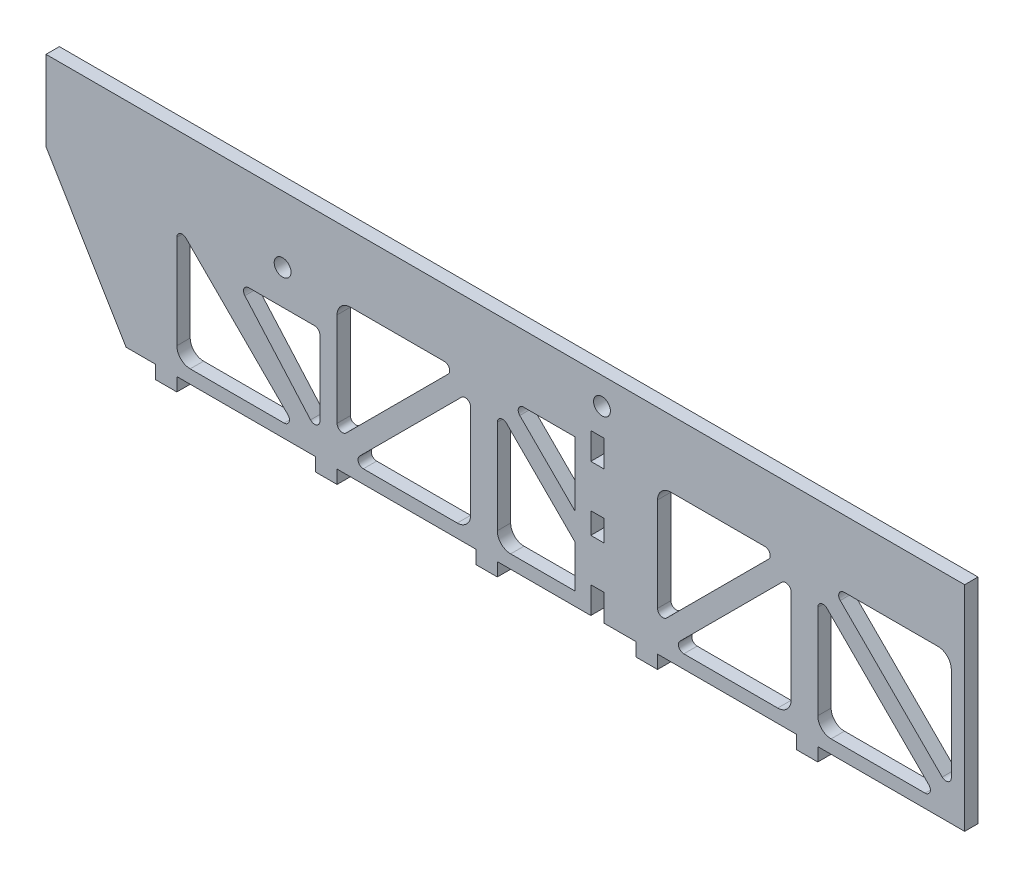
SolidWorks part; units mm, degrees
material "Pine"
ref_plane "Front Plane" through (0, 0, 0) normal (0, 0, 1) x (1, 0, 0)
ref_plane "Top Plane" through (0, 0, 0) normal (0, 1, 0) x (1, 0, 0)
ref_plane "Right Plane" through (0, 0, 0) normal (1, 0, 0) x (0, 0, -1)
sketch "Model" plane through (0, 0, 0) normal (0, 0, 1) x (1, 0, 0)
  line L0 (-306.6281, 15.625) -> (-306.6281, 51.1493)
  line L1 (-309.1681, 53.6893) -> (-340.406, 53.6893)
  line L2 (-342.3135, 49.472) -> (-311.0755, 13.9477)
  line L8 (-171.2321, 6.35) -> (-215.9, 6.35)
  line L9 (-222.25, 57.3679) -> (-222.25, 12.7)
  line L10 (-217.9139, 59.1639) -> (-169.4361, 10.6861)
  line L11 (-234.95, 57.3679) -> (-234.95, 12.7)
  line L12 (-241.3, 6.35) -> (-285.9679, 6.35)
  line L13 (-239.2861, 59.1639) -> (-287.7639, 10.6861)
  line L14 (-294.1139, 17.0361) -> (-245.6361, 65.5139)
  line L15 (-298.45, 63.5) -> (-298.45, 18.8321)
  line L16 (-247.4321, 69.85) -> (-292.1, 69.85)
  line L17 (-323.6321, 6.35) -> (-368.3, 6.35)
  line L18 (-374.65, 57.3679) -> (-374.65, 12.7)
  line L19 (-370.3139, 59.1639) -> (-321.8361, 10.6861)
  line L20 (-18.8321, 6.35) -> (-63.5, 6.35)
  line L21 (-69.85, 57.3679) -> (-69.85, 12.7)
  line L22 (-17.0361, 10.6861) -> (-65.5139, 59.1639)
  line L23 (-82.55, 57.3679) -> (-82.55, 12.7)
  line L24 (-88.9, 6.35) -> (-133.5679, 6.35)
  line L25 (-86.8861, 59.1639) -> (-135.3639, 10.6861)
  line L26 (-93.2361, 65.5139) -> (-141.7139, 17.0361)
  line L27 (-146.05, 63.5) -> (-146.05, 18.8321)
  line L28 (-95.0321, 69.85) -> (-139.7, 69.85)
  line L29 (-163.0861, 17.0361) -> (-211.5639, 65.5139)
  line L30 (-165.1, 69.85) -> (-209.7679, 69.85)
  line L31 (-158.75, 63.5) -> (-158.75, 18.8321)
  line L35 (-398.78, 0) -> (-436.88, 63.5)
  line L36 (0, 0) -> (-398.78, 0)
  line L37 (0, 0) -> (0, 95.25)
  line L38 (0, 95.25) -> (-436.88, 95.25)
  line L39 (-436.88, 63.5) -> (-436.88, 95.25)
  line L40 (-6.35, 63.5) -> (-6.35, 18.8321)
  line L41 (-59.1639, 65.5139) -> (-10.6861, 17.0361)
  line L42 (-12.7, 69.85) -> (-57.3679, 69.85)
  arc A0 (-222.25, 12.7) -> (-215.9, 6.35) centre (-215.9, 12.7) ccw
  arc A1 (-217.9139, 59.1639) -> (-222.25, 57.3679) centre (-219.71, 57.3679) ccw
  arc A2 (-171.2321, 6.35) -> (-169.4361, 10.6861) centre (-171.2321, 8.89) ccw
  arc A3 (-234.95, 57.3679) -> (-239.2861, 59.1639) centre (-237.49, 57.3679) ccw
  arc A4 (-241.3, 6.35) -> (-234.95, 12.7) centre (-241.3, 12.7) ccw
  arc A5 (-287.7639, 10.6861) -> (-285.9679, 6.35) centre (-285.9679, 8.89) ccw
  arc A6 (-245.6361, 65.5139) -> (-247.4321, 69.85) centre (-247.4321, 67.31) ccw
  arc A7 (-298.45, 18.8321) -> (-294.1139, 17.0361) centre (-295.91, 18.8321) ccw
  arc A8 (-292.1, 69.85) -> (-298.45, 63.5) centre (-292.1, 63.5) ccw
  arc A9 (-323.6321, 6.35) -> (-321.8361, 10.6861) centre (-323.6321, 8.89) ccw
  arc A10 (-374.65, 12.7) -> (-368.3, 6.35) centre (-368.3, 12.7) ccw
  arc A11 (-370.3139, 59.1639) -> (-374.65, 57.3679) centre (-372.11, 57.3679) ccw
  arc A12 (-69.85, 12.7) -> (-63.5, 6.35) centre (-63.5, 12.7) ccw
  arc A13 (-65.5139, 59.1639) -> (-69.85, 57.3679) centre (-67.31, 57.3679) ccw
  arc A14 (-18.8321, 6.35) -> (-17.0361, 10.6861) centre (-18.8321, 8.89) ccw
  arc A15 (-82.55, 57.3679) -> (-86.8861, 59.1639) centre (-85.09, 57.3679) ccw
  arc A16 (-88.9, 6.35) -> (-82.55, 12.7) centre (-88.9, 12.7) ccw
  arc A17 (-135.3639, 10.6861) -> (-133.5679, 6.35) centre (-133.5679, 8.89) ccw
  arc A18 (-93.2361, 65.5139) -> (-95.0321, 69.85) centre (-95.0321, 67.31) ccw
  arc A19 (-146.05, 18.8321) -> (-141.7139, 17.0361) centre (-143.51, 18.8321) ccw
  arc A20 (-139.7, 69.85) -> (-146.05, 63.5) centre (-139.7, 63.5) ccw
  arc A21 (-163.0861, 17.0361) -> (-158.75, 18.8321) centre (-161.29, 18.8321) ccw
  arc A22 (-209.7679, 69.85) -> (-211.5639, 65.5139) centre (-209.7679, 67.31) ccw
  arc A23 (-158.75, 63.5) -> (-165.1, 69.85) centre (-165.1, 63.5) ccw
  arc A24 (-306.6281, 15.625) -> (-311.0755, 13.9477) centre (-309.1681, 15.625) cw
  arc A25 (-340.406, 53.6893) -> (-342.3135, 49.472) centre (-340.406, 51.1493) ccw
  arc A26 (-306.6281, 51.1493) -> (-309.1681, 53.6893) centre (-309.1681, 51.1493) ccw
  arc A27 (-10.6861, 17.0361) -> (-6.35, 18.8321) centre (-8.89, 18.8321) ccw
  arc A28 (-57.3679, 69.85) -> (-59.1639, 65.5139) centre (-57.3679, 67.31) ccw
  arc A29 (-6.35, 63.5) -> (-12.7, 69.85) centre (-12.7, 63.5) ccw
  circle A30 centre (-172.466, 88.9) radius 4
  circle A31 centre (-324.358, 70.104) radius 4
  dimension "D2" = 172.466
  dimension "D4" = 8
  dimension "D5" = 151.892
  dimension "D7" = 8
  dimension "D6" = 18.796
  dimension "D8" = 2.54
  dimension "D1" = 95.25
  dimension "D3" = 6.35
extrude "Boss-Extrude1" add sketch "Model" along normal blind 6.35
sketch "Sketch1" plane through (0, 0, 6.35) normal (0, 0, 1) x (1, 0, 0)
  line L0 (-69.85, 95.25) -> (-69.85, 0) construction
  line L1 (-69.85, 57.3679) -> (-69.85, 12.7) construction
  line L2 (-398.78, 0) -> (0, 0) construction
  line L3 (-146.05, 95.25) -> (-146.05, 0) construction
  line L4 (-146.05, 63.5) -> (-146.05, 18.8321) construction
  line L5 (-222.25, 95.25) -> (-222.25, 0) construction
  line L6 (-222.25, 57.3679) -> (-222.25, 12.7) construction
  line L7 (-298.45, 95.25) -> (-298.45, 0) construction
  line L8 (-298.45, 63.5) -> (-298.45, 18.8321) construction
  line L9 (-374.65, 95.25) -> (-374.65, 0) construction
  line L10 (-374.65, 57.3679) -> (-374.65, 12.7) construction
  line L11 (0, 95.25) -> (-436.88, 95.25) construction
  line L12 (-69.85, 0) -> (-80.01, 0)
  line L13 (-69.85, 0) -> (-69.85, -6.35)
  line L14 (-69.85, -6.35) -> (-80.01, -6.35)
  line L15 (-80.01, 0) -> (-80.01, -6.35)
  line L16 (-146.05, 0) -> (-156.21, 0)
  line L17 (-146.05, 0) -> (-146.05, -6.35)
  line L18 (-146.05, -6.35) -> (-156.21, -6.35)
  line L19 (-156.21, 0) -> (-156.21, -6.35)
  line L20 (-222.25, 0) -> (-232.41, 0)
  line L21 (-222.25, 0) -> (-222.25, -6.35)
  line L22 (-222.25, -6.35) -> (-232.41, -6.35)
  line L23 (-232.41, 0) -> (-232.41, -6.35)
  line L24 (-298.45, 0) -> (-308.61, 0)
  line L25 (-298.45, 0) -> (-298.45, -6.35)
  line L26 (-298.45, -6.35) -> (-308.61, -6.35)
  line L27 (-308.61, 0) -> (-308.61, -6.35)
  line L28 (-374.65, 0) -> (-384.81, 0)
  line L29 (-374.65, 0) -> (-374.65, -6.35)
  line L30 (-374.65, -6.35) -> (-384.81, -6.35)
  line L31 (-384.81, 0) -> (-384.81, -6.35)
  line L32 (0, 0) -> (0, 95.25) construction
  line L53 (-436.88, 95.25) -> (0, 95.25)
  line L54 (-436.88, 95.25) -> (-436.88, 101.6)
  line L55 (-436.88, 101.6) -> (0, 101.6)
  line L56 (0, 95.25) -> (0, 101.6)
  dimension "D1" = 6.35
  dimension "D2" = 10.16
  dimension "D3" = 10.16
  dimension "D4" = 10.16
  dimension "D5" = 10.16
  dimension "D6" = 10.16
  dimension "D8" = 6.35
extrude "Boss-Extrude2" add sketch "Sketch1" against normal up to surface (6.35 mm away) up to face at (-168.466, 88.9, 0)
sketch "Sketch2" plane through (0, 0, 0) normal (0, 0, -1) x (-1, 0, 0)
  line L0 (158.75, 18.8321) -> (158.75, 63.5) construction
  line L1 (185.42, 69.85) -> (165.1, 69.85)
  line L2 (185.42, 69.85) -> (185.42, 0)
  line L3 (185.42, 0) -> (165.1, 0)
  line L4 (165.1, 69.85) -> (165.1, 0)
  line L6 (222.25, 0) -> (156.21, 0) construction
  line L8 (165.1, 69.85) -> (209.7679, 69.85) construction
  line L10 (156.21, -6.35) -> (146.05, -6.35) construction
  line L11 (177.8, 0) -> (171.45, 0)
  line L12 (177.8, 0) -> (177.8, 12.7)
  line L13 (177.8, 12.7) -> (171.45, 12.7)
  line L14 (171.45, 0) -> (171.45, 12.7)
  line L15 (177.8, 33.02) -> (171.45, 33.02)
  line L16 (177.8, 33.02) -> (177.8, 43.18)
  line L17 (177.8, 43.18) -> (171.45, 43.18)
  line L18 (171.45, 33.02) -> (171.45, 43.18)
  line L19 (177.8, 63.5) -> (171.45, 63.5)
  line L20 (177.8, 63.5) -> (177.8, 76.2)
  line L21 (177.8, 76.2) -> (171.45, 76.2)
  line L22 (171.45, 63.5) -> (171.45, 76.2)
  dimension "D1" = 6.35
  dimension "D2" = 20.32
  dimension "D3" = 10.16
  dimension "D4" = 12.7
  dimension "D5" = 6.35
  dimension "D6" = 20.32
  dimension "D7" = 20.32
  dimension "D8" = 12.7
  dimension "D9" = 6.35
  dimension "D10" = 6.35
extrude "Boss-Extrude3" add sketch "Sketch2" against normal up to surface (6.35 mm away) contours L4 | L19 L22 L1 L4 L3 L14 L13 L12 L2 L20 L15 L18 L17 L16 region at (-184.6925, 34.925, 0) up to face at (-319.4123, 39.5294, 6.35)
extrude "Cut-Extrude1" cut sketch "Sketch2<3>" against normal blind 6.35 contours L22 L1 L20 L21 | L14 L3 L12 L13 region at (-174.625, 73.025, 0) region at (-174.625, 6.35, 0)
sketch "Sketch2<3>" plane through (0, 0, 0) normal (0, 0, -1) x (-1, 0, 0) same geometry as "Sketch2"
sketch "Sketch3" plane through (0, 0, 0) normal (0, 0, -1) x (-1, 0, 0)
  line L1 (154.4024, 72.7027) -> (167.3891, 72.7027)
  line L2 (154.4024, 72.7027) -> (154.4024, 13.591)
  line L3 (154.4024, 13.591) -> (167.3891, 13.591)
  line L4 (167.3891, 72.7027) -> (167.3891, 13.591)
extrude "Boss-Extrude4" add sketch "Sketch3" against normal up to surface (6.35 mm away) up to face at (-224.7462, 7.8828, 6.35)
equation "\"thick\"=0.25"
equation "\"D1@Boss-Extrude1\"=\"thick\""
